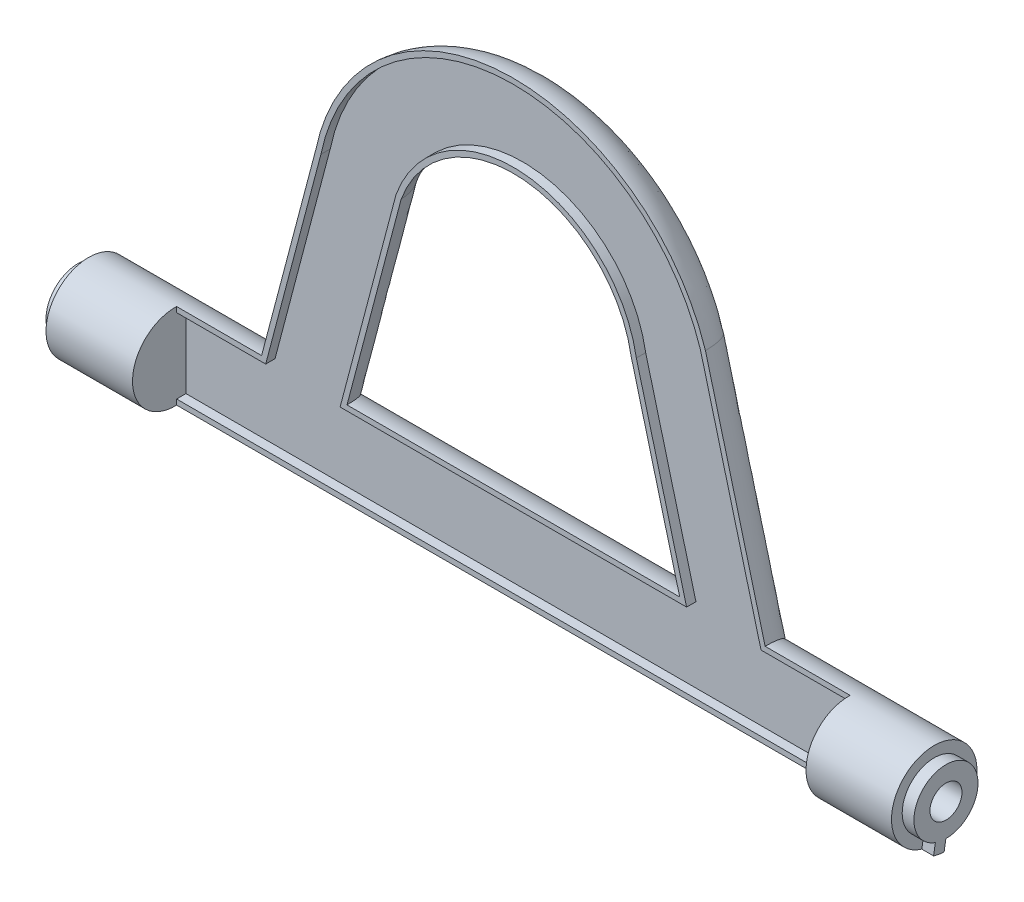
SolidWorks part; units mm, degrees
material "ABS PC"
ref_plane "Piano frontale" through (0, 0, 0) normal (0, 0, 1) x (1, 0, 0)
ref_plane "Piano superiore" through (0, 0, 0) normal (0, 1, 0) x (1, 0, 0)
ref_plane "Piano destro" through (0, 0, 0) normal (1, 0, 0) x (0, 0, -1)
sketch "Schizzo1" plane through (0, 0, 0) normal (1, 0, 0) x (0, 0, -1)
  circle A0 centre (0, 0) radius 4
  dimension "D1" = 8
extrude "Estrusione-Estrusione1" add sketch "Schizzo1" along normal mid plane 81.25
sketch "Schizzo2" plane through (0, 0, 0) normal (0, 0, 1) x (1, 0, 0)
  line L0 (-39.2686, 0) -> (39.72, 0) construction
  line L1 (-20.625, 0) -> (-14.5039, 23.2063)
  line L2 (20.625, 0) -> (14.5039, 23.2063)
  line L3 (40.625, -4) -> (40.625, 4) construction
  line L4 (-40.625, 4) -> (-40.625, -4) construction
  arc A0 (-14.5039, 23.2063) -> (14.5039, 23.2063) centre (0, 19.3806) cw
  point P7 (0, 34.3806)
  dimension "D1" = 20
  dimension "D2" = 20
  dimension "D3" = 15
  dimension "D4" = 24
sketch "Schizzo3" plane through (0, 0, 0) normal (0, 1, 0) x (1, 0, 0)
  circle A0 centre (-20.625, 0) radius 4
  dimension "D1" = 8
sweep "Sweep1" add profiles "Schizzo3" path "Schizzo2"
sketch "Schizzo4" plane through (0, 0, 0) normal (1, 0, 0) x (0, 0, -1)
  line L6 (-4, 0) -> (4, 0) construction
  line L10 (-0.0099, -3) -> (-0.1742, -3.9962) construction
  line L17 (-0.0099, -3) -> (-0.1742, -3.9962)
  line L18 (-1.16, -3.8281) -> (-0.9954, -2.8301)
  line L19 (-0.9954, -2.8301) -> (-1.16, -3.8281) construction
  circle A15 centre (0, 0) radius 4 construction
  arc A16 (-0.1742, -3.9962) -> (-1.16, -3.8281) centre (0, 0) ccw
  arc A17 (-0.0099, -3) -> (-0.9954, -2.8301) centre (0, 0) ccw
  circle A18 centre (0, 0) radius 4 construction
  circle A19 centre (0, 0) radius 3 construction
  point P6 (0, 0)
  dimension "D3" = 1
  dimension "D1" = 6
  dimension "D2" = 1
  dimension "D4" = 0.9954
  dimension "D5" = 1.16
extrude "Taglio-Estrusione1" cut sketch "Schizzo4" against normal blind 1.1 from surface contours A17 L17 A16 L18 starting at face at (40.625, 0, -4)
sketch "Schizzo5" plane through (0, 0, 0) normal (1, 0, 0) x (0, 0, -1)
  line L6 (-1.16, -3.8281) -> (-0.9954, -2.8301)
  line L9 (-0.0099, -3) -> (-0.1742, -3.9962)
  line L10 (-1.16, -3.8281) -> (-0.9954, -2.8301)
  line L11 (-0.0099, -3) -> (-0.1742, -3.9962)
  arc A10 (-0.0099, -3) -> (-0.9954, -2.8301) centre (0, 0) ccw
  arc A11 (-0.1742, -3.9962) -> (-1.16, -3.8281) centre (0, 0) ccw
  arc A12 (-0.0099, -3) -> (-0.9954, -2.8301) centre (0, 0) ccw
  arc A13 (-0.1742, -3.9962) -> (-1.16, -3.8281) centre (0, 0) ccw
  dimension "D1" = 0
extrude "Taglio-Estrusione2" cut sketch "Schizzo5" along normal blind 1 from surface starting at face at (-40.625, 0, -4)
sketch "Schizzo6" plane through (0, 0, 0) normal (1, 0, 0) x (0, 0, -1)
  circle A0 centre (0, 0) radius 1.5
  dimension "D1" = 3
extrude "Taglio-Estrusione3" cut sketch "Schizzo6" along normal blind 6 from surface starting at face at (-40.625, -1.9535, 0.3331)
sketch "Schizzo7" plane through (0, 0, 0) normal (1, 0, 0) x (0, 0, -1)
  circle A0 centre (0, 0) radius 1.5 construction
  circle A1 centre (0, 0) radius 1.5
extrude "Taglio-Estrusione4" cut sketch "Schizzo7" against normal blind 6 from surface starting at face at (40.625, -1.9535, 0.3331)
sketch "Schizzo8" plane through (0, 0, 0) normal (0, 0, 1) x (1, 0, 0)
  line L0 (39.525, 4) -> (23.5699, 4) construction
  line L2 (-31.525, -3.5) -> (31.525, -3.5)
  line L3 (-31.525, -3.5) -> (-31.525, 3.5)
  line L5 (-31.525, 3.5) -> (-23.1847, 3.5)
  line L8 (31.525, -3.5) -> (31.525, 3.5)
  line L9 (-31.525, -3.5) -> (31.525, 3.5) construction
  line L10 (-31.525, 3.5) -> (31.525, -3.5) construction
  line L13 (39.525, -4) -> (39.525, 4) construction
  line L15 (23.5699, 4) -> (17.9836, 25.1792) construction
  line L18 (11.0243, 21.2334) -> (15.5699, 4) construction
  line L19 (-15.5699, 4) -> (-10.5039, 23.2063) construction
  line L42 (-18.5039, 23.2063) -> (-23.5699, 4) construction
  line L43 (23.5699, 4) -> (17.9836, 25.1792) construction
  line L44 (11.0243, 21.2334) -> (15.5699, 4) construction
  line L45 (-15.5699, 4) -> (-10.5039, 23.2063) construction
  line L46 (-18.5039, 23.2063) -> (-23.5699, 4) construction
  line L47 (23.0865, 3.8725) -> (17.5036, 25.0385)
  line L48 (-18.017, 23.0919) -> (-23.0865, 3.8725)
  line L49 (-16.0534, 4.1275) -> (-10.9816, 23.3557)
  line L50 (11.5136, 21.3391) -> (16.0534, 4.1275)
  line L51 (-23.0865, 3.8725) -> (-23.1847, 3.5)
  line L52 (-16.0534, 4.1275) -> (-16.2189, 3.5)
  line L53 (16.0534, 4.1275) -> (16.2189, 3.5)
  line L54 (23.0865, 3.8725) -> (23.1847, 3.5)
  line L55 (-16.2189, 3.5) -> (16.2189, 3.5)
  line L56 (23.1847, 3.5) -> (31.525, 3.5)
  arc A1 (11.0243, 21.2334) -> (-10.5039, 23.2063) centre (0, 19.3806) ccw construction
  arc A3 (17.9836, 25.1792) -> (-18.5039, 23.2063) centre (0, 19.3806) ccw construction
  arc A6 (11.0243, 21.2334) -> (-10.5039, 23.2063) centre (0, 19.3806) ccw construction
  arc A7 (17.9836, 25.1792) -> (-18.5039, 23.2063) centre (0, 19.3806) ccw construction
  arc A8 (17.5036, 25.0385) -> (-18.017, 23.0919) centre (0, 19.3806) ccw
  arc A9 (11.5136, 21.3391) -> (-10.9816, 23.3557) centre (0, 19.3806) ccw
  point P0 (0, 0)
  dimension "D1" = 0.5
  dimension "D2" = 8
  dimension "D3" = 0.5
  dimension "D4" = 0.5
extrude "Taglio-Estrusione5" cut sketch "Schizzo8" against normal blind 6 from offset 5
sketch "Schizzo9" plane through (0, 0, 0) normal (0, 1, 0) x (1, 0, 0)
  line L1 (-31.525, -4) -> (31.525, -4)
  line L2 (-31.525, -4) -> (-31.525, 0.127)
  line L3 (-31.525, 0.127) -> (31.525, 0.127)
  line L4 (31.525, -4) -> (31.525, 0.127)
  line L5 (31.525, 1) -> (31.525, -1.9365) construction
  line L6 (-31.525, -1.9365) -> (-23.2018, -1.9365) construction
  line L7 (-31.525, 1) -> (-31.525, -1.9365) construction
  point P6 (-31.525, -1.9365)
extrude "Taglio-Estrusione7" cut sketch "Schizzo9" against normal through all both and the other way through all
